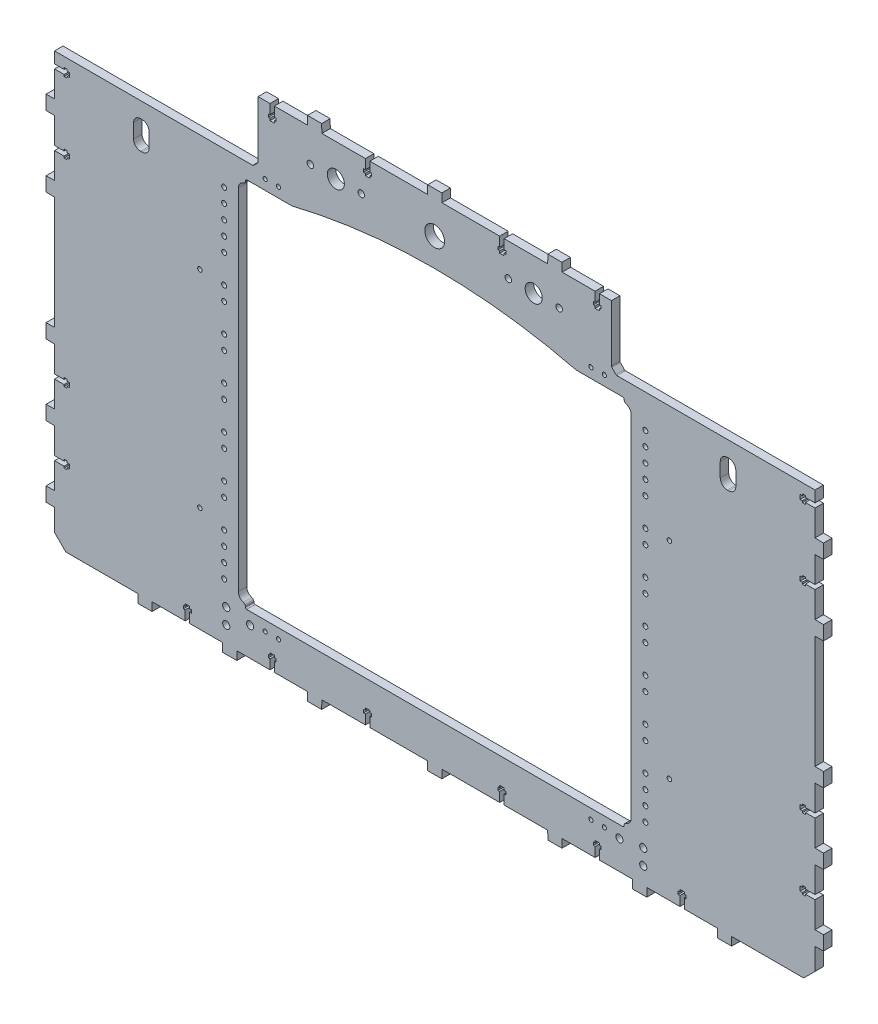
SolidWorks part; units mm, degrees
material "Клен"
ref_plane "Front" through (0, 0, 0) normal (0, 0, 1) x (1, 0, 0)
ref_plane "Top" through (0, 0, 0) normal (0, 1, 0) x (1, 0, 0)
ref_plane "Right" through (0, 0, 0) normal (1, 0, 0) x (0, 0, -1)
sketch "Эскиз1" plane through (0, 0, 0) normal (0, 0, 1) x (1, 0, 0)
  line L0 (1859.5805, 14.5374) -> (1859.5805, 267.5072) construction
  line L1 (1846.6822, 122.5572) -> (1912.7745, 122.5572) construction
  line L2 (1846.6822, 268.5572) -> (1912.7745, 268.5572) construction
  line L3 (1859.5805, 267.5072) -> (1859.5805, 273.1347) construction
  line L6 (1560.5805, 76.7865) -> (1826.5797, 76.7865)
  line L7 (1827.5797, 78.0783) -> (1827.5797, 77.7865)
  line L8 (1832.5805, 332.0072) -> (1832.5797, 84.7865)
  line L9 (1827.5805, 339.0072) -> (1827.5805, 338.7154)
  line L10 (1826.5805, 340.0072) -> (1793.6805, 340.0072)
  line L11 (1560.5805, 340.0072) -> (1592.5638, 340.0072)
  line L13 (1559.5805, 339.0072) -> (1559.5805, 338.7154)
  line L15 (1554.5805, 84.7865) -> (1554.5805, 332.0072)
  line L17 (1559.5805, 78.0783) -> (1559.5805, 77.7865)
  line L18 (1524.5805, 401.0072) -> (1524.5805, 24.1014) construction
  line L19 (1862.5805, 416.6106) -> (1862.5805, 5.7676) construction
  line L20 (1424.5805, 401.0072) -> (1424.5805, 24.1014) construction
  line L21 (1962.5805, 416.6106) -> (1962.5805, 5.7676) construction
  line L22 (1433.5805, 343.0572) -> (1435.0805, 343.0572)
  line L23 (1433.5805, 289.9572) -> (1433.5805, 288.7572)
  line L24 (1433.5805, 149.9572) -> (1433.5805, 148.7572)
  line L25 (1424.5805, 121.4072) -> (1424.5805, 103.0572)
  line L26 (1431.3805, 293.0572) -> (1431.3805, 294.2572)
  line L27 (1431.3805, 154.2572) -> (1433.5805, 154.2572)
  line L28 (1418.5805, 71.5072) -> (1424.5805, 71.4072)
  line L29 (1418.5805, 321.5072) -> (1418.5805, 311.5072)
  line L30 (1418.5805, 311.5072) -> (1424.5805, 311.4072)
  line L31 (1424.5805, 149.9572) -> (1424.5805, 131.6072)
  line L32 (1418.5805, 81.5072) -> (1418.5805, 71.5072)
  line L33 (1433.5805, 338.7572) -> (1431.3805, 338.7572)
  line L34 (1424.5805, 293.0572) -> (1431.3805, 293.0572)
  line L35 (1424.5805, 153.0572) -> (1431.3805, 153.0572)
  line L36 (1433.5805, 103.0572) -> (1435.0805, 103.0572)
  line L37 (1424.5805, 99.9572) -> (1424.5805, 81.6072)
  line L38 (1424.5805, 321.6072) -> (1418.5805, 321.5072)
  line L39 (1433.5805, 293.0572) -> (1435.0805, 293.0572)
  line L40 (1433.5805, 148.7572) -> (1431.3805, 148.7572)
  line L41 (1435.0805, 343.0572) -> (1435.0805, 339.9572)
  line L42 (1431.3805, 289.9572) -> (1424.5805, 289.9572)
  line L43 (1424.5805, 181.6072) -> (1418.5805, 181.5072)
  line L44 (1431.3805, 103.0572) -> (1431.3805, 104.2572)
  line L45 (1435.0805, 103.0572) -> (1435.0805, 99.9572)
  line L46 (1431.3805, 343.0572) -> (1431.3805, 344.2572)
  line L47 (1424.5805, 261.4072) -> (1424.5805, 181.6072)
  line L48 (1433.5805, 153.0572) -> (1435.0805, 153.0572)
  line L49 (1424.5805, 103.0572) -> (1431.3805, 103.0572)
  line L50 (1433.5805, 104.2572) -> (1433.5805, 103.0572)
  line L51 (1424.5805, 311.4072) -> (1424.5805, 293.0572)
  line L52 (1433.5805, 294.2572) -> (1433.5805, 293.0572)
  line L53 (1424.5805, 131.6072) -> (1418.5805, 131.5072)
  line L54 (1431.3805, 338.7572) -> (1431.3805, 339.9572)
  line L55 (1418.5805, 271.5072) -> (1418.5805, 261.5072)
  line L56 (1433.5805, 154.2572) -> (1433.5805, 153.0572)
  line L57 (1433.5805, 98.7572) -> (1431.3805, 98.7572)
  line L58 (1424.5805, 81.6072) -> (1418.5805, 81.5072)
  line L59 (1424.5805, 343.0572) -> (1431.3805, 343.0572)
  line L60 (1431.3805, 339.9572) -> (1424.5805, 339.9572)
  line L61 (1435.0805, 289.9572) -> (1433.5805, 289.9572)
  line L62 (1431.3805, 148.7572) -> (1431.3805, 149.9572)
  line L63 (1435.0805, 339.9572) -> (1433.5805, 339.9572)
  line L64 (1431.3805, 294.2572) -> (1433.5805, 294.2572)
  line L65 (1424.5805, 289.9572) -> (1424.5805, 271.6072)
  line L66 (1433.5805, 99.9572) -> (1433.5805, 98.7572)
  line L67 (1431.3805, 98.7572) -> (1431.3805, 99.9572)
  line L68 (1433.5805, 344.2572) -> (1433.5805, 343.0572)
  line L69 (1424.5805, 271.6072) -> (1418.5805, 271.5072)
  line L70 (1435.0805, 153.0572) -> (1435.0805, 149.9572)
  line L71 (1424.5805, 71.4072) -> (1424.5805, 56.0072)
  line L72 (1431.3805, 344.2572) -> (1433.5805, 344.2572)
  line L73 (1435.0805, 293.0572) -> (1435.0805, 289.9572)
  line L74 (1433.5805, 288.7572) -> (1431.3805, 288.7572)
  line L75 (1418.5805, 131.5072) -> (1418.5805, 121.5072)
  line L76 (1435.0805, 99.9572) -> (1433.5805, 99.9572)
  line L77 (1424.5805, 351.0072) -> (1424.5805, 343.0572)
  line L78 (1418.5805, 171.5072) -> (1424.5805, 171.4072)
  line L79 (1418.5805, 121.5072) -> (1424.5805, 121.4072)
  line L80 (1431.3805, 104.2572) -> (1433.5805, 104.2572)
  line L81 (1431.3805, 288.7572) -> (1431.3805, 289.9572)
  line L82 (1424.5805, 171.4072) -> (1424.5805, 153.0572)
  line L83 (1431.3805, 149.9572) -> (1424.5805, 149.9572)
  line L84 (1433.5805, 339.9572) -> (1433.5805, 338.7572)
  line L85 (1418.5805, 261.5072) -> (1424.5805, 261.4072)
  line L86 (1418.5805, 181.5072) -> (1418.5805, 171.5072)
  line L87 (1431.3805, 99.9572) -> (1424.5805, 99.9572)
  line L88 (1424.5805, 339.9572) -> (1424.5805, 321.6072)
  line L89 (1431.3805, 153.0572) -> (1431.3805, 154.2572)
  line L90 (1435.0805, 149.9572) -> (1433.5805, 149.9572)
  line L91 (1424.5805, 56.0072) -> (1432.5805, 48.0072)
  line L92 (1424.5805, 351.0072) -> (1524.5805, 351.0072)
  line L93 (1432.5805, 48.0072) -> (1483.4805, 48.0072)
  line L94 (1953.5805, 99.9572) -> (1952.0805, 99.9572)
  line L95 (1955.7805, 154.2572) -> (1955.7805, 153.0572)
  line L96 (1953.5805, 289.9572) -> (1952.0805, 289.9572)
  line L97 (1953.5805, 343.0572) -> (1953.5805, 344.2572)
  line L98 (1962.5805, 99.9572) -> (1955.7805, 99.9572)
  line L99 (1955.7805, 153.0572) -> (1962.5805, 153.0572)
  line L100 (1953.5805, 294.2572) -> (1955.7805, 294.2572)
  line L101 (1955.7805, 338.7572) -> (1953.5805, 338.7572)
  line L102 (1953.5805, 103.0572) -> (1953.5805, 104.2572)
  line L103 (1952.0805, 153.0572) -> (1953.5805, 153.0572)
  line L104 (1955.7805, 288.7572) -> (1953.5805, 288.7572)
  line L105 (1962.5805, 321.6072) -> (1962.5805, 339.9572)
  line L106 (1955.7805, 344.2572) -> (1955.7805, 343.0572)
  line L107 (1968.5805, 131.5072) -> (1962.5805, 131.6072)
  line L108 (1962.5805, 149.9572) -> (1955.7805, 149.9572)
  line L109 (1968.5805, 261.5072) -> (1968.5805, 271.5072)
  line L110 (1962.5805, 289.9572) -> (1955.7805, 289.9572)
  line L111 (1955.7805, 343.0572) -> (1962.5805, 343.0572)
  line L112 (1952.0805, 99.9572) -> (1952.0805, 103.0572)
  line L113 (1955.7805, 149.9572) -> (1955.7805, 148.7572)
  line L114 (1952.0805, 293.0572) -> (1953.5805, 293.0572)
  line L115 (1953.5805, 339.9572) -> (1952.0805, 339.9572)
  line L116 (1962.5805, 56.0072) -> (1962.5805, 71.4072)
  line L117 (1955.7805, 103.0572) -> (1962.5805, 103.0572)
  line L118 (1968.5805, 181.5072) -> (1962.5805, 181.6072)
  line L119 (1955.7805, 293.0572) -> (1962.5805, 293.0572)
  line L120 (1953.5805, 344.2572) -> (1955.7805, 344.2572)
  line L121 (1962.5805, 71.4072) -> (1968.5805, 71.5072)
  line L122 (1962.5805, 131.6072) -> (1962.5805, 149.9572)
  line L123 (1968.5805, 171.5072) -> (1968.5805, 181.5072)
  line L124 (1968.5805, 271.5072) -> (1962.5805, 271.6072)
  line L125 (1953.5805, 104.2572) -> (1955.7805, 104.2572)
  line L126 (1953.5805, 153.0572) -> (1953.5805, 154.2572)
  line L127 (1953.5805, 293.0572) -> (1953.5805, 294.2572)
  line L128 (1953.5805, 98.7572) -> (1953.5805, 99.9572)
  line L129 (1962.5805, 121.4072) -> (1968.5805, 121.5072)
  line L130 (1962.5805, 261.4072) -> (1968.5805, 261.5072)
  line L131 (1952.0805, 289.9572) -> (1952.0805, 293.0572)
  line L132 (1952.0805, 343.0572) -> (1953.5805, 343.0572)
  line L133 (1968.5805, 81.5072) -> (1962.5805, 81.6072)
  line L134 (1955.7805, 148.7572) -> (1953.5805, 148.7572)
  line L135 (1962.5805, 293.0572) -> (1962.5805, 311.4072)
  line L136 (1952.0805, 339.9572) -> (1952.0805, 343.0572)
  line L137 (1955.7805, 98.7572) -> (1953.5805, 98.7572)
  line L138 (1962.5805, 103.0572) -> (1962.5805, 121.4072)
  line L139 (1962.5805, 181.6072) -> (1962.5805, 261.4072)
  line L140 (1962.5805, 311.4072) -> (1968.5805, 311.5072)
  line L141 (1952.0805, 103.0572) -> (1953.5805, 103.0572)
  line L142 (1955.7805, 294.2572) -> (1955.7805, 293.0572)
  line L143 (1962.5805, 339.9572) -> (1955.7805, 339.9572)
  line L144 (1955.7805, 104.2572) -> (1955.7805, 103.0572)
  line L145 (1953.5805, 154.2572) -> (1955.7805, 154.2572)
  line L146 (1955.7805, 289.9572) -> (1955.7805, 288.7572)
  line L147 (1968.5805, 121.5072) -> (1968.5805, 131.5072)
  line L148 (1953.5805, 288.7572) -> (1953.5805, 289.9572)
  line L149 (1955.7805, 339.9572) -> (1955.7805, 338.7572)
  line L150 (1954.5805, 48.0072) -> (1962.5805, 56.0072)
  line L151 (1962.5805, 81.6072) -> (1962.5805, 99.9572)
  line L152 (1953.5805, 149.9572) -> (1952.0805, 149.9572)
  line L153 (1962.5805, 171.4072) -> (1968.5805, 171.5072)
  line L154 (1968.5805, 311.5072) -> (1968.5805, 321.5072)
  line L155 (1955.7805, 99.9572) -> (1955.7805, 98.7572)
  line L156 (1952.0805, 149.9572) -> (1952.0805, 153.0572)
  line L157 (1962.5805, 271.6072) -> (1962.5805, 289.9572)
  line L158 (1968.5805, 321.5072) -> (1962.5805, 321.6072)
  line L159 (1962.5805, 343.0572) -> (1962.5805, 351.0072)
  line L160 (1968.5805, 71.5072) -> (1968.5805, 81.5072)
  line L161 (1953.5805, 148.7572) -> (1953.5805, 149.9572)
  line L162 (1962.5805, 153.0572) -> (1962.5805, 171.4072)
  line L163 (1953.5805, 338.7572) -> (1953.5805, 339.9572)
  line L164 (1862.5805, 351.0072) -> (1962.5805, 351.0072)
  line L165 (1954.5805, 48.0072) -> (1903.6805, 48.0072)
  line L166 (1325.5433, 339.9572) -> (1983.9894, 339.9572) construction
  line L169 (1693.5113, 412.8647) -> (1693.5113, 297.5072) construction
  line L170 (1900.5405, 339.9572) -> (1901.5405, 339.9572)
  line L171 (1895.5405, 334.9572) -> (1895.5405, 324.9572)
  line L172 (1900.5405, 319.9572) -> (1901.5405, 319.9572)
  line L173 (1906.5405, 334.9572) -> (1906.5405, 324.9572)
  line L176 (1486.4822, 319.9572) -> (1485.4822, 319.9572)
  line L177 (1480.4822, 334.9572) -> (1480.4822, 324.9572)
  line L178 (1486.4822, 339.9572) -> (1485.4822, 339.9572)
  line L179 (1491.4822, 334.9572) -> (1491.4822, 324.9572)
  line L180 (1893.4805, 48.0072) -> (1893.5805, 42.0072)
  line L181 (1867.0305, 58.5072) -> (1870.1305, 58.5072)
  line L182 (1903.5805, 42.0072) -> (1903.6805, 48.0072)
  line L183 (1867.0305, 54.8072) -> (1865.8305, 54.8072)
  line L184 (1870.1305, 58.5072) -> (1870.1305, 57.0072)
  line L185 (1871.3305, 54.8072) -> (1870.1305, 54.8072)
  line L186 (1865.8305, 57.0072) -> (1867.0305, 57.0072)
  line L187 (1871.3305, 57.0072) -> (1871.3305, 54.8072)
  line L188 (1867.0305, 48.0072) -> (1867.0305, 54.8072)
  line L189 (1870.1305, 57.0072) -> (1871.3305, 57.0072)
  line L190 (1870.1305, 54.8072) -> (1870.1305, 48.0072)
  line L192 (1865.8305, 54.8072) -> (1865.8305, 57.0072)
  line L193 (1893.5805, 42.0072) -> (1903.5805, 42.0072)
  line L194 (1867.0305, 57.0072) -> (1867.0305, 58.5072)
  line L195 (1867.0305, 48.0072) -> (1854.5805, 48.0072)
  line L196 (1893.4805, 48.0072) -> (1870.1305, 48.0072)
  line L197 (1493.5805, 42.0072) -> (1493.6805, 48.0072)
  line L198 (1521.3305, 57.0072) -> (1521.3305, 54.8072)
  line L199 (1517.0305, 48.0072) -> (1517.0305, 54.8072)
  line L200 (1483.5805, 42.0072) -> (1493.5805, 42.0072)
  line L201 (1515.8305, 57.0072) -> (1517.0305, 57.0072)
  line L202 (1521.3305, 54.8072) -> (1520.1305, 54.8072)
  line L203 (1483.4805, 48.0072) -> (1483.5805, 42.0072)
  line L204 (1517.0305, 57.0072) -> (1517.0305, 58.5072)
  line L205 (1517.0305, 58.5072) -> (1520.1305, 58.5072)
  line L206 (1517.0305, 54.8072) -> (1515.8305, 54.8072)
  line L207 (1520.1305, 54.8072) -> (1520.1305, 48.0072)
  line L209 (1520.1305, 58.5072) -> (1520.1305, 57.0072)
  line L210 (1520.1305, 57.0072) -> (1521.3305, 57.0072)
  line L211 (1515.8305, 54.8072) -> (1515.8305, 57.0072)
  line L212 (1520.1305, 48.0072) -> (1532.5805, 48.0072)
  line L213 (1493.6805, 48.0072) -> (1517.0305, 48.0072)
  line L552 (1568.2876, 354.2143) -> (1565.3733, 351.3001)
  line L553 (1564.6662, 351.0072) -> (1524.5805, 351.0072)
  line L624 (1532.5805, 48.0072) -> (1543.4805, 48.0072)
  line L625 (1543.4805, 48.0072) -> (1543.5805, 42.0072)
  line L626 (1543.5805, 42.0072) -> (1553.5805, 42.0072)
  line L627 (1553.5805, 42.0072) -> (1553.6805, 48.0072)
  line L628 (1553.6805, 48.0072) -> (1577.0305, 48.0072)
  line L629 (1577.0305, 48.0072) -> (1577.0305, 54.8072)
  line L630 (1577.0305, 54.8072) -> (1575.8305, 54.8072)
  line L631 (1575.8305, 54.8072) -> (1575.8305, 57.0072)
  line L632 (1575.8305, 57.0072) -> (1577.0305, 57.0072)
  line L633 (1577.0305, 57.0072) -> (1577.0305, 58.5072)
  line L634 (1577.0305, 58.5072) -> (1580.1305, 58.5072)
  line L635 (1580.1305, 58.5072) -> (1580.1305, 57.0072)
  line L636 (1580.1305, 57.0072) -> (1581.3305, 57.0072)
  line L637 (1581.3305, 57.0072) -> (1581.3305, 54.8072)
  line L638 (1581.3305, 54.8072) -> (1580.1305, 54.8072)
  line L639 (1580.1305, 54.8072) -> (1580.1305, 48.0072)
  line L640 (1580.1305, 48.0072) -> (1603.4805, 48.0072)
  line L641 (1603.4805, 48.0072) -> (1603.5805, 42.0072)
  line L642 (1603.5805, 42.0072) -> (1613.5805, 42.0072)
  line L643 (1613.5805, 42.0072) -> (1613.6805, 48.0072)
  line L644 (1613.6805, 48.0072) -> (1644.5305, 48.0072)
  line L645 (1644.5305, 48.0072) -> (1644.5305, 54.8072)
  line L646 (1644.5305, 54.8072) -> (1643.3305, 54.8072)
  line L647 (1643.3305, 54.8072) -> (1643.3305, 57.0072)
  line L648 (1643.3305, 57.0072) -> (1644.5305, 57.0072)
  line L649 (1644.5305, 57.0072) -> (1644.5305, 58.5072)
  line L650 (1644.5305, 58.5072) -> (1647.6305, 58.5072)
  line L651 (1647.6305, 58.5072) -> (1647.6305, 57.0072)
  line L652 (1647.6305, 57.0072) -> (1648.8305, 57.0072)
  line L653 (1648.8305, 57.0072) -> (1648.8305, 54.8072)
  line L654 (1648.8305, 54.8072) -> (1647.6305, 54.8072)
  line L655 (1647.6305, 54.8072) -> (1647.6305, 48.0072)
  line L656 (1647.6305, 48.0072) -> (1688.4805, 48.0072)
  line L657 (1688.4805, 48.0072) -> (1688.5805, 42.0072)
  line L658 (1688.5805, 42.0072) -> (1698.5805, 42.0072)
  line L659 (1698.5805, 42.0072) -> (1698.6805, 48.0072)
  line L660 (1698.6805, 48.0072) -> (1739.5305, 48.0072)
  line L661 (1739.5305, 48.0072) -> (1739.5305, 54.8072)
  line L662 (1739.5305, 54.8072) -> (1738.3305, 54.8072)
  line L663 (1738.3305, 54.8072) -> (1738.3305, 57.0072)
  line L664 (1738.3305, 57.0072) -> (1739.5305, 57.0072)
  line L665 (1739.5305, 57.0072) -> (1739.5305, 58.5072)
  line L666 (1739.5305, 58.5072) -> (1742.6305, 58.5072)
  line L667 (1742.6305, 58.5072) -> (1742.6305, 57.0072)
  line L668 (1742.6305, 57.0072) -> (1743.8305, 57.0072)
  line L669 (1743.8305, 57.0072) -> (1743.8305, 54.8072)
  line L670 (1743.8305, 54.8072) -> (1742.6305, 54.8072)
  line L671 (1742.6305, 54.8072) -> (1742.6305, 48.0072)
  line L672 (1742.6305, 48.0072) -> (1773.4805, 48.0072)
  line L673 (1773.4805, 48.0072) -> (1773.5805, 42.0072)
  line L674 (1773.5805, 42.0072) -> (1783.5805, 42.0072)
  line L675 (1783.5805, 42.0072) -> (1783.6805, 48.0072)
  line L676 (1783.6805, 48.0072) -> (1807.0305, 48.0072)
  line L677 (1807.0305, 48.0072) -> (1807.0305, 54.8072)
  line L678 (1807.0305, 54.8072) -> (1805.8305, 54.8072)
  line L679 (1805.8305, 54.8072) -> (1805.8305, 57.0072)
  line L680 (1805.8305, 57.0072) -> (1807.0305, 57.0072)
  line L681 (1807.0305, 57.0072) -> (1807.0305, 58.5072)
  line L682 (1807.0305, 58.5072) -> (1810.1305, 58.5072)
  line L683 (1810.1305, 58.5072) -> (1810.1305, 57.0072)
  line L684 (1810.1305, 57.0072) -> (1811.3305, 57.0072)
  line L685 (1811.3305, 57.0072) -> (1811.3305, 54.8072)
  line L686 (1811.3305, 54.8072) -> (1810.1305, 54.8072)
  line L687 (1810.1305, 54.8072) -> (1810.1305, 48.0072)
  line L688 (1810.1305, 48.0072) -> (1833.4805, 48.0072)
  line L689 (1833.4805, 48.0072) -> (1833.5805, 42.0072)
  line L690 (1833.5805, 42.0072) -> (1843.5805, 42.0072)
  line L691 (1843.5805, 42.0072) -> (1843.6805, 48.0072)
  line L692 (1843.6805, 48.0072) -> (1854.5805, 48.0072)
  line L763 (1862.5805, 351.0072) -> (1822.4947, 351.0072)
  line L764 (1821.7876, 351.3001) -> (1818.8733, 354.2143)
  line L765 (1818.5805, 354.9215) -> (1818.5805, 395.0072)
  line L766 (1818.5805, 395.0072) -> (1810.1305, 395.0072)
  line L767 (1810.1305, 395.0072) -> (1810.1305, 388.2072)
  line L768 (1810.1305, 388.2072) -> (1811.3305, 388.2072)
  line L769 (1811.3305, 388.2072) -> (1811.3305, 386.0072)
  line L770 (1811.3305, 386.0072) -> (1810.1305, 386.0072)
  line L771 (1810.1305, 386.0072) -> (1810.1305, 384.5072)
  line L772 (1810.1305, 384.5072) -> (1807.0305, 384.5072)
  line L773 (1807.0305, 384.5072) -> (1807.0305, 386.0072)
  line L774 (1807.0305, 386.0072) -> (1805.8305, 386.0072)
  line L775 (1805.8305, 386.0072) -> (1805.8305, 388.2072)
  line L776 (1805.8305, 388.2072) -> (1807.0305, 388.2072)
  line L777 (1807.0305, 388.2072) -> (1807.0305, 395.0072)
  line L778 (1807.0305, 395.0072) -> (1783.6805, 395.0072)
  line L779 (1783.6805, 395.0072) -> (1783.5805, 401.0072)
  line L780 (1783.5805, 401.0072) -> (1773.5805, 401.0072)
  line L781 (1773.5805, 401.0072) -> (1773.4805, 395.0072)
  line L782 (1773.4805, 395.0072) -> (1742.6305, 395.0072)
  line L783 (1742.6305, 395.0072) -> (1742.6305, 388.2072)
  line L784 (1742.6305, 388.2072) -> (1743.8305, 388.2072)
  line L785 (1743.8305, 388.2072) -> (1743.8305, 386.0072)
  line L786 (1743.8305, 386.0072) -> (1742.6305, 386.0072)
  line L787 (1742.6305, 386.0072) -> (1742.6305, 384.5072)
  line L788 (1742.6305, 384.5072) -> (1739.5305, 384.5072)
  line L789 (1739.5305, 384.5072) -> (1739.5305, 386.0072)
  line L790 (1739.5305, 386.0072) -> (1738.3305, 386.0072)
  line L791 (1738.3305, 386.0072) -> (1738.3305, 388.2072)
  line L792 (1738.3305, 388.2072) -> (1739.5305, 388.2072)
  line L793 (1739.5305, 388.2072) -> (1739.5305, 395.0072)
  line L794 (1739.5305, 395.0072) -> (1698.6805, 395.0072)
  line L795 (1698.6805, 395.0072) -> (1698.5805, 401.0072)
  line L796 (1698.5805, 401.0072) -> (1688.5805, 401.0072)
  line L797 (1688.5805, 401.0072) -> (1688.4805, 395.0072)
  line L798 (1688.4805, 395.0072) -> (1647.6305, 395.0072)
  line L799 (1647.6305, 395.0072) -> (1647.6305, 388.2072)
  line L800 (1647.6305, 388.2072) -> (1648.8305, 388.2072)
  line L801 (1648.8305, 388.2072) -> (1648.8305, 386.0072)
  line L802 (1648.8305, 386.0072) -> (1647.6305, 386.0072)
  line L803 (1647.6305, 386.0072) -> (1647.6305, 384.5072)
  line L804 (1647.6305, 384.5072) -> (1644.5305, 384.5072)
  line L805 (1644.5305, 384.5072) -> (1644.5305, 386.0072)
  line L806 (1644.5305, 386.0072) -> (1643.3305, 386.0072)
  line L807 (1643.3305, 386.0072) -> (1643.3305, 388.2072)
  line L808 (1643.3305, 388.2072) -> (1644.5305, 388.2072)
  line L809 (1644.5305, 388.2072) -> (1644.5305, 395.0072)
  line L810 (1644.5305, 395.0072) -> (1613.6805, 395.0072)
  line L811 (1613.6805, 395.0072) -> (1613.5805, 401.0072)
  line L812 (1613.5805, 401.0072) -> (1603.5805, 401.0072)
  line L813 (1603.5805, 401.0072) -> (1603.4805, 395.0072)
  line L814 (1603.4805, 395.0072) -> (1580.1305, 395.0072)
  line L815 (1580.1305, 395.0072) -> (1580.1305, 388.2072)
  line L816 (1580.1305, 388.2072) -> (1581.3305, 388.2072)
  line L817 (1581.3305, 388.2072) -> (1581.3305, 386.0072)
  line L818 (1581.3305, 386.0072) -> (1580.1305, 386.0072)
  line L819 (1580.1305, 386.0072) -> (1580.1305, 384.5072)
  line L820 (1580.1305, 384.5072) -> (1577.0305, 384.5072)
  line L821 (1577.0305, 384.5072) -> (1577.0305, 386.0072)
  line L822 (1577.0305, 386.0072) -> (1575.8305, 386.0072)
  line L823 (1575.8305, 386.0072) -> (1575.8305, 388.2072)
  line L824 (1575.8305, 388.2072) -> (1577.0305, 388.2072)
  line L825 (1577.0305, 388.2072) -> (1577.0305, 395.0072)
  line L826 (1577.0305, 395.0072) -> (1568.5805, 395.0072)
  line L827 (1568.5805, 395.0072) -> (1568.5805, 354.9215)
  circle A0 centre (1859.5805, 268.5572) radius 1.6
  circle A1 centre (1859.5805, 122.5572) radius 1.6
  circle A2 centre (1527.4422, 268.5572) radius 1.6
  circle A3 centre (1527.4422, 122.5572) radius 1.6
  arc A4 (1901.5405, 319.9572) -> (1906.5405, 324.9572) centre (1901.5405, 324.9572) ccw
  arc A5 (1895.5405, 324.9572) -> (1900.5405, 319.9572) centre (1900.5405, 324.9572) ccw
  arc A6 (1901.5405, 339.9572) -> (1906.5405, 334.9572) centre (1901.5405, 334.9572) cw
  arc A7 (1900.5405, 339.9572) -> (1895.5405, 334.9572) centre (1900.5405, 334.9572) ccw
  arc A8 (1568.2876, 354.2143) -> (1568.5805, 354.9215) centre (1567.5805, 354.9215) ccw
  arc A9 (1564.6662, 351.0072) -> (1565.3733, 351.3001) centre (1564.6662, 352.0072) ccw
  arc A10 (1821.7876, 351.3001) -> (1822.4947, 351.0072) centre (1822.4947, 352.0072) ccw
  arc A11 (1818.5805, 354.9215) -> (1818.8733, 354.2143) centre (1819.5805, 354.9215) ccw
  circle A28 centre (1544.5805, 177.5072) radius 1.75
  circle A29 centre (1544.5805, 147.5072) radius 1.75
  circle A30 centre (1544.5805, 137.5072) radius 1.75
  circle A31 centre (1544.5805, 117.5072) radius 1.75
  circle A32 centre (1544.5805, 107.5072) radius 1.75
  circle A33 centre (1544.5805, 97.5072) radius 1.75
  circle A34 centre (1544.5805, 87.5072) radius 1.75
  circle A35 centre (1546.0805, 71.0072) radius 2.55
  circle A36 centre (1546.0805, 60.0072) radius 2.55
  circle A37 centre (1544.5805, 197.5072) radius 1.75
  circle A38 centre (1544.5805, 207.5072) radius 1.75
  circle A39 centre (1544.5805, 227.5072) radius 1.75
  circle A40 centre (1544.5805, 237.5072) radius 1.75
  circle A41 centre (1544.5805, 257.5072) radius 1.75
  circle A42 centre (1544.5805, 267.5072) radius 1.75
  circle A43 centre (1544.5805, 287.5072) radius 1.75
  circle A44 centre (1544.5805, 297.5072) radius 1.75
  circle A45 centre (1544.5805, 307.5072) radius 1.75
  circle A46 centre (1544.5805, 317.5072) radius 1.75
  circle A47 centre (1544.5805, 327.5072) radius 1.75
  circle A87 centre (1573.5805, 347.0072) radius 1.5
  circle A88 centre (1583.0805, 347.0072) radius 1.5
  circle A89 centre (1605.5805, 372.0072) radius 2.3
  circle A90 centre (1623.5805, 372.0072) radius 6.05
  circle A91 centre (1641.5805, 372.0072) radius 2.3
  circle A92 centre (1693.5113, 372.0072) radius 7
  circle A93 centre (1745.5805, 372.0072) radius 2.3
  circle A94 centre (1763.5805, 372.0072) radius 6.05
  circle A95 centre (1781.5805, 372.0072) radius 2.3
  circle A96 centre (1804.0805, 347.0072) radius 1.5
  circle A97 centre (1813.5805, 347.0072) radius 1.5
  circle A98 centre (1842.5805, 327.5072) radius 1.75
  circle A99 centre (1842.5805, 317.5072) radius 1.75
  circle A100 centre (1842.5805, 307.5072) radius 1.75
  circle A101 centre (1842.5805, 297.5072) radius 1.75
  circle A102 centre (1842.5805, 287.5072) radius 1.75
  circle A103 centre (1842.5805, 267.5072) radius 1.75
  circle A104 centre (1842.5805, 257.5072) radius 1.75
  circle A105 centre (1842.5805, 237.5072) radius 1.75
  circle A106 centre (1842.5805, 227.5072) radius 1.75
  circle A107 centre (1842.5805, 207.5072) radius 1.75
  circle A108 centre (1842.5805, 197.5072) radius 1.75
  circle A109 centre (1842.5805, 177.5072) radius 1.75
  circle A110 centre (1842.5805, 167.5072) radius 1.75
  circle A111 centre (1842.5805, 147.5072) radius 1.75
  circle A112 centre (1842.5805, 137.5072) radius 1.75
  circle A113 centre (1842.5805, 117.5072) radius 1.75
  circle A114 centre (1842.5805, 107.5072) radius 1.75
  circle A115 centre (1842.5805, 97.5072) radius 1.75
  circle A116 centre (1842.5805, 87.5072) radius 1.75
  circle A117 centre (1841.0805, 71.0072) radius 2.55
  circle A118 centre (1841.0805, 60.0072) radius 2.55
  circle A119 centre (1824.2277, 68.2968) radius 2.55
  circle A120 centre (1813.5805, 69.7865) radius 1.5
  circle A121 centre (1804.0805, 69.7865) radius 1.5
  circle A122 centre (1583.0805, 69.7865) radius 1.5
  circle A123 centre (1573.5805, 69.7865) radius 1.5
  circle A124 centre (1562.9305, 68.2968) radius 2.55
  circle A125 centre (1544.5805, 167.5072) radius 1.75
  arc A133 (1826.5797, 76.7865) -> (1827.5797, 77.7865) centre (1826.5797, 77.7865) ccw
  arc A134 (1829.0083, 79.995) -> (1827.5797, 78.0783) centre (1829.5797, 78.0783) ccw
  arc A135 (1829.0083, 79.995) -> (1832.5797, 84.7865) centre (1827.5797, 84.7865) ccw
  arc A136 (1832.5805, 332.0072) -> (1829.009, 336.7988) centre (1827.5805, 332.0072) ccw
  arc A137 (1827.5805, 338.7154) -> (1829.009, 336.7988) centre (1829.5805, 338.7154) ccw
  arc A138 (1827.5805, 339.0072) -> (1826.5805, 340.0072) centre (1826.5805, 339.0072) ccw
  arc A139 (1793.6805, 340.0072) -> (1592.5638, 340.0072) centre (1693.1221, -70.0562) ccw
  arc A141 (1560.5805, 340.0072) -> (1559.5805, 339.0072) centre (1560.5805, 339.0072) ccw
  arc A143 (1558.1519, 336.7988) -> (1559.5805, 338.7154) centre (1557.5805, 338.7154) ccw
  arc A145 (1558.1519, 336.7988) -> (1554.5805, 332.0072) centre (1559.5805, 332.0072) ccw
  arc A147 (1559.5805, 77.7865) -> (1560.5805, 76.7865) centre (1560.5805, 77.7865) ccw
  arc A149 (1554.5805, 84.7865) -> (1558.1519, 79.995) centre (1559.5805, 84.7865) ccw
  arc A151 (1559.5805, 78.0783) -> (1558.1519, 79.995) centre (1557.5805, 78.0783) ccw
  arc A152 (1485.4822, 319.9572) -> (1480.4822, 324.9572) centre (1485.4822, 324.9572) cw
  arc A153 (1485.4822, 339.9572) -> (1480.4822, 334.9572) centre (1485.4822, 334.9572) ccw
  arc A154 (1491.4822, 324.9572) -> (1486.4822, 319.9572) centre (1486.4822, 324.9572) cw
  arc A155 (1486.4822, 339.9572) -> (1491.4822, 334.9572) centre (1486.4822, 334.9572) cw
  point P18 (1892.325, 329.9572)
  dimension "D7" = 5
  dimension "D11" = 3.2
  dimension "D12" = 3.2
  dimension "D2" = 100
  dimension "D3" = 100
  dimension "D8" = 3
  dimension "D9" = 74.55
  dimension "D10" = 146
extrude "Бобышка-Вытянуть1" add sketch "Эскиз1" along normal blind 6
